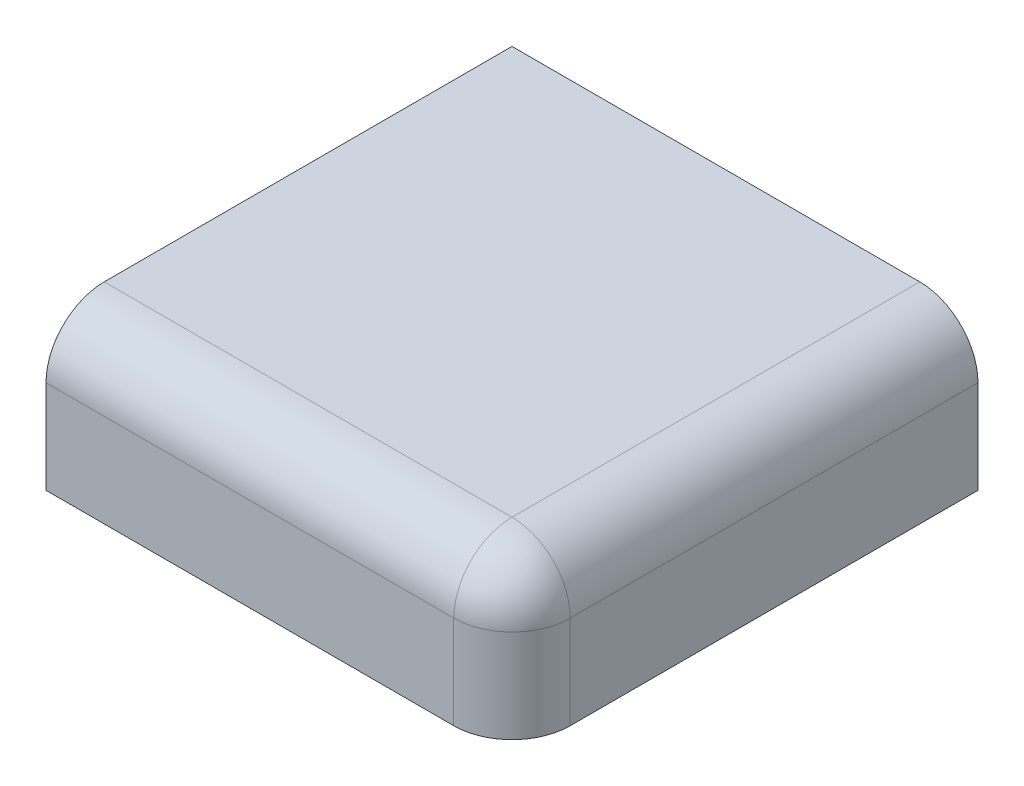
SolidWorks part; units mm, degrees
ref_plane "Front Plane" through (0, 0, 0) normal (0, 0, 1) x (1, 0, 0)
ref_plane "Top Plane" through (0, 0, 0) normal (0, 1, 0) x (1, 0, 0)
ref_plane "Right Plane" through (0, 0, 0) normal (1, 0, 0) x (0, 0, -1)
sketch "Эскиз1" plane through (0, 0, 0) normal (0, 1, 0) x (1, 0, 0)
  line L0 (-20, -20) -> (20, -20)
  line L1 (-20, -20) -> (-20, 20)
  line L2 (20, -20) -> (20, 20)
  line L3 (-20, 20) -> (20, 20)
  line L4 (-20, -20) -> (20, 20) construction
  line L5 (20, -20) -> (-20, 20) construction
  point P1 (0, 0)
  dimension "D1" = 40
  dimension "D2" = 40
extrude "Бобышка-Вытянуть1" add sketch "Эскиз1" against normal blind 13
sketch "Эскиз7" plane through (-20, 0, 0) normal (-1, 0, 0) x (0, 0, 1)
  line L1 (-28.759, -6.5) -> (30.1285, -6.5) construction
  line L2 (-20, 0) -> (20, 0) construction
  line L3 (-20, -13) -> (20, -13) construction
  line L4 (0, 5.2438) -> (0, -20.548) construction
  line L5 (0, -2.1098) -> (-2.0375, -3.2861)
  line L6 (0, -2.1098) -> (2.0375, -3.2861)
  circle A0 centre (0, -6.8152) radius 4.075
  point P0 (0, 0)
  point P15 (0, -10.8902)
  dimension "D2" = 8.15
  dimension "D1" = 60
extrude "Вырез-Вытянуть2" cut sketch "Эскиз7" against normal blind 2.15 contours A0 | A0 L6 L5 region at (-20, -2.6034, 0) region at (-20, -6.8152, 0)
pattern_circular "Круговой массив1" count 2 over 90 about axis through (0, -13, 0) along (0, -1, 0) of "Вырез-Вытянуть2"
fillet "Скругление2" radius 5 3 edges at (0, 0, 20) (20, 0, 0) (20, -6.5, 20)
